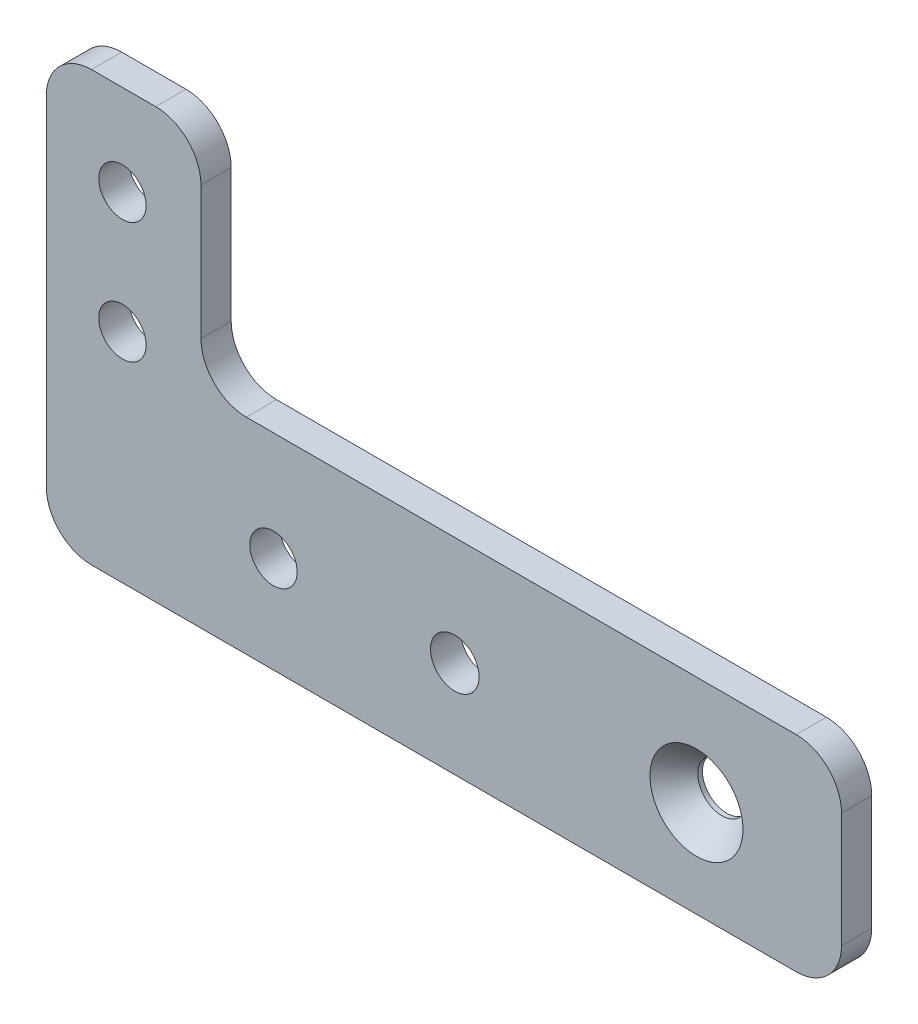
SolidWorks part; units mm, degrees
material "6061-T6 (SS)"
ref_plane "Front Plane" through (0, 0, 0) normal (0, 0, 1) x (1, 0, 0)
ref_plane "Top Plane" through (0, 0, 0) normal (0, 1, 0) x (1, 0, 0)
ref_plane "Right Plane" through (0, 0, 0) normal (1, 0, 0) x (0, 0, -1)
sketch "Sketch1" plane through (0, 0, 0) normal (0, 0, 1) x (1, 0, 0)
  line L0 (-21.59, 23.8125) -> (-37.846, 23.8125) construction
  line L1 (-45.72, -23.8125) -> (45.72, -23.8125)
  line L2 (-45.72, -23.8125) -> (-45.72, 23.8125)
  line L3 (-45.72, 23.8125) -> (45.72, 23.8125)
  line L4 (45.72, -23.8125) -> (45.72, 23.8125)
  line L5 (-45.72, -23.8125) -> (45.72, 23.8125) construction
  line L6 (-45.72, 23.8125) -> (45.72, -23.8125) construction
  line L7 (45.72, 23.8125) -> (-21.59, 23.8125)
  line L8 (45.72, 23.8125) -> (45.72, 0.3175)
  line L9 (45.72, 0.3175) -> (-21.59, 0.3175)
  line L10 (-21.59, 23.8125) -> (-21.59, 0.3175)
  line L11 (-45.72, -23.8125) -> (-37.846, -23.8125)
  line L12 (-45.72, -23.8125) -> (-45.72, 23.8125)
  line L13 (-45.72, 23.8125) -> (-37.846, 23.8125)
  line L14 (-37.846, -23.8125) -> (-37.846, 23.8125)
  line L15 (-37.846, -23.8125) -> (45.72, -23.8125)
  line L16 (-37.846, -23.8125) -> (-37.846, -21.2725)
  line L17 (-37.846, -21.2725) -> (45.72, -21.2725)
  line L18 (45.72, -23.8125) -> (45.72, -21.2725)
  line L19 (-21.59, 23.8125) -> (-37.846, 23.8125) construction
  line L20 (-29.845, 23.8125) -> (-29.845, -21.2725) construction
  circle A0 centre (-29.845, -11.1125) radius 2.4892
  circle A1 centre (-29.845, 1.5875) radius 2.4892
  circle A2 centre (-29.845, 14.2875) radius 2.4892
  circle A4 centre (-13.97, -11.1125) radius 2.4892
  circle A5 centre (5.08, -11.1125) radius 2.5527
  circle A7 centre (30.48, -11.1125) radius 2.5527
  point P0 (0, 0)
  dimension "D7" = 15.875
  dimension "D18" = 5.1054
  dimension "D19" = 4.9784
  dimension "D13" = 25.4
  dimension "D8" = 50.8
  dimension "D1" = 91.44
  dimension "D2" = 9.525
  dimension "D3" = 24.13
  dimension "D4" = 24.13
  dimension "D5" = 7.874
  dimension "D6" = 47.625
  dimension "D9" = 12.7
  dimension "D10" = 12.7
  dimension "D11" = 12.7
  dimension "D12" = 15.875
  dimension "D16" = 2.54
extrude "Boss-Extrude1" add sketch "Sketch1" along normal blind 3.175 contours L14 L17 L4 L9 L10 L3 A5 A4 A2 A1 A0 | A0 region at (-1.432, -6.6351, 0) region at (-29.845, -11.1125, 0)
fillet "Fillet1" radius 4.7625 6 edges at (-37.846, 23.8125, 1.5875) (-21.59, 23.8125, 1.5875) (-21.59, 0.3175, 1.5875) (45.72, 0.3175, 1.5875) (45.72, -21.2725, 1.5875) (-37.846, -21.2725, 1.5875)
hole_wizard "CSK for #10 Flat Head Machine Screw1" positions "Sketch3" profile "Sketch4" countersink size "#10" standard "ANSI Inch"
sketch "Sketch3" plane through (0, 0, 3.175) normal (0, 0, 1) x (1, 0, 0)
  point P0 (30.48, -11.1125)
sketch "Sketch4" plane through (30.48, -11.1125, 3.175) normal (1, 0, 0) x (0, -1, 0)
  line L0 (0, 0) -> (0, 20.5838)
  line L1 (0, 20.5838) -> (2.5527, 19.05)
  line L2 (2.5527, 19.05) -> (2.5527, 2.6882)
  line L3 (2.5527, 2.6882) -> (4.8895, 0)
  line L5 (4.8895, 0) -> (0, 0)
  line L6 (-2.5527, 2.6882) -> (-4.8895, 0) construction
  line L10 (0, 20.5838) -> (-2.5527, 19.05) construction
  line L11 (0, -6.35) -> (0, 107.95) construction
  dimension "Hole Dia." = 5.1054
  dimension "Hole Depth" = 19.05
  dimension "Near C'Sink Dia." = 9.779
  dimension "Near C'Sink Angle" = 82
  dimension "Drill Angle" = 118
